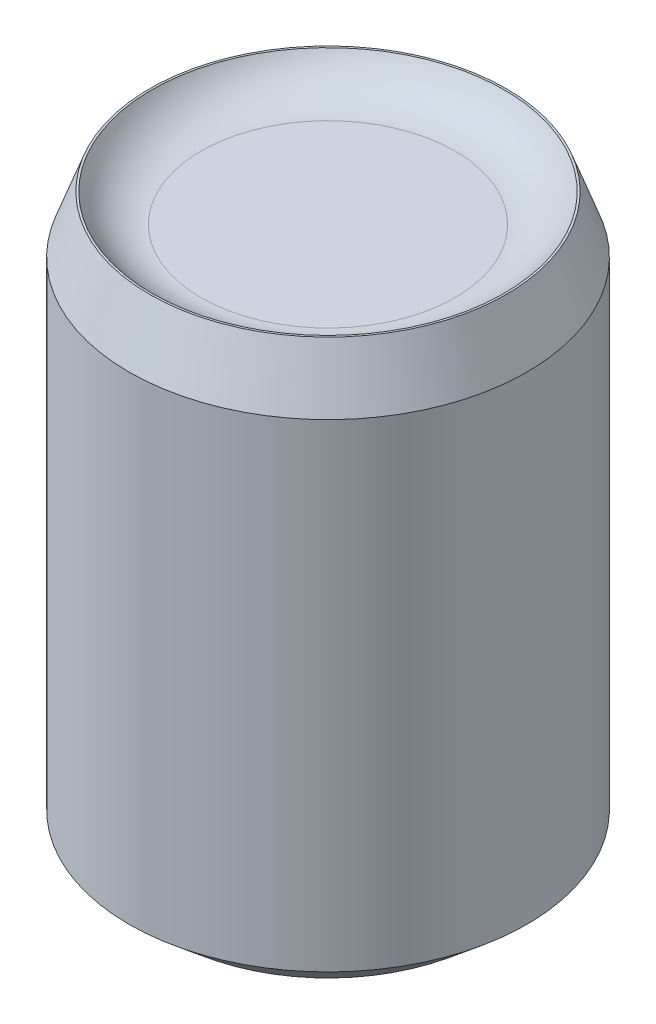
SolidWorks part; units mm, degrees
ref_plane "Front Plane" through (0, 0, 0) normal (0, 0, 1) x (1, 0, 0)
ref_plane "Top Plane" through (0, 0, 0) normal (0, 1, 0) x (1, 0, 0)
ref_plane "Right Plane" through (0, 0, 0) normal (1, 0, 0) x (0, 0, -1)
sketch "Sketch1" plane through (0, 0, 0) normal (0, 1, 0) x (1, 0, 0)
  circle A0 centre (0, 0) radius 35
extrude "Boss-Extrude1" add sketch "Sketch1" along normal blind 100
chamfer "Chamfer1" distance 10 angle 20 1 edges at (0, 100, 35) first distance on face at (0, 100, 35)
chamfer "Chamfer2" distance 7 angle 40 1 edges at (0, 0, 35) first distance on face at (0, 0, 35)
sketch "Sketch2" plane through (0, 100, 0) normal (0, 1, 0) x (1, 0, 0)
  circle A0 centre (0, 0) radius 31
extrude "Cut-Extrude1" cut sketch "Sketch2" against normal blind 5
fillet "Fillet1" radius 10 1 edges at (0, 95, 31)
